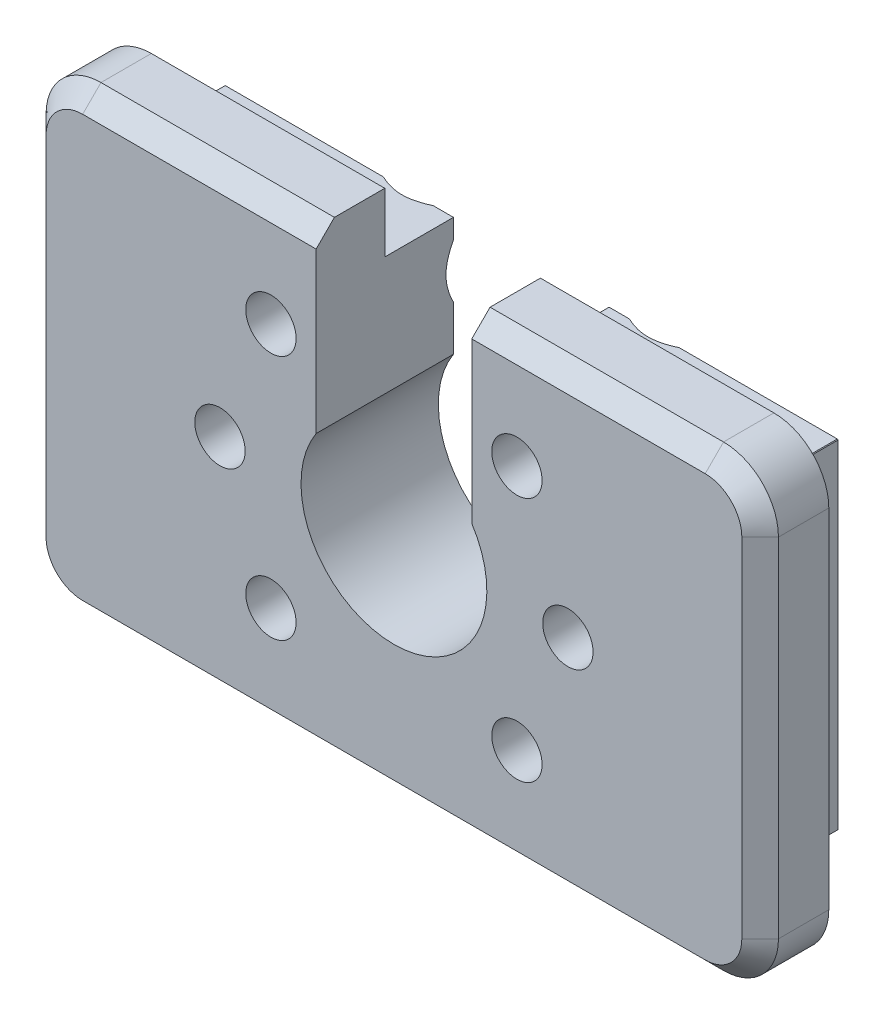
SolidWorks part; units mm, degrees
material "PET"
ref_plane "Front Plane" through (0, 0, 0) normal (0, 0, 1) x (1, 0, 0)
ref_plane "Top Plane" through (0, 0, 0) normal (0, 1, 0) x (1, 0, 0)
ref_plane "Right Plane" through (0, 0, 0) normal (1, 0, 0) x (0, 0, -1)
sketch "Sketch1" plane through (0, 0, 0) normal (0, 0, 1) x (1, 0, 0)
  line L1 (40, -25) -> (-40, -25)
  line L2 (40, -25) -> (40, 25)
  line L3 (40, 25) -> (-40, 25)
  line L4 (-40, -25) -> (-40, 25)
  line L5 (40, -25) -> (-40, 25) construction
  line L6 (40, 25) -> (-40, -25) construction
  point P0 (0, 0)
  dimension "D1" = 50
  dimension "D2" = 80
extrude "Boss-Extrude1" add sketch "Sketch1" against normal blind 7.5
sketch "Sketch2" plane through (0, 0, -7.5) normal (0, 0, -1) x (-1, 0, 0)
  line L8 (33.5, -18.5) -> (33.5, 18.5)
  line L9 (33.5, 18.5) -> (-33.5, 18.5)
  line L10 (-33.5, 18.5) -> (-33.5, -18.5)
  line L11 (-33.5, -18.5) -> (33.5, -18.5)
  line L12 (33.5, -18.5) -> (33.5, 18.5)
  line L13 (33.5, 18.5) -> (-33.5, 18.5)
  line L14 (-33.5, 18.5) -> (-33.5, -18.5)
  line L15 (-33.5, -18.5) -> (33.5, -18.5)
  dimension "D1" = 6.5
extrude "Boss-Extrude2" add sketch "Sketch2" along normal blind 7.5
sketch "Sketch3" plane through (0, 0, 0) normal (0, 0, 1) x (1, 0, 0)
  line L0 (0, 0) -> (0, 51.1675) construction
  line L1 (40, 25) -> (-40, 25) construction
  line L2 (8.5, 5.5473) -> (-8.5, 5.5473) construction
  line L3 (8.5, 5.5473) -> (8.5, 25)
  line L4 (8.5, 25) -> (-8.5, 25)
  line L5 (-8.5, 5.5473) -> (-8.5, 25)
  line L6 (8.5, 5.5473) -> (-8.5, 25) construction
  line L7 (8.5, 25) -> (-8.5, 5.5473) construction
  line L8 (0, 0) -> (-19, 0) construction
  arc A0 (-8.5, 5.5473) -> (8.5, 5.5473) centre (0, 0) ccw
  circle A1 centre (-19, 0) radius 2.75
  circle A2 centre (-13.435, 13.435) radius 2.75
  circle A3 centre (0, 19) radius 2.75 construction
  circle A4 centre (13.435, 13.435) radius 2.75
  circle A5 centre (19, 0) radius 2.75
  circle A6 centre (13.435, -13.435) radius 2.75
  circle A7 centre (0, -19) radius 2.75 construction
  circle A8 centre (-13.435, -13.435) radius 2.75
  point P3 (0, 15.2736)
  point P28 (0, 0)
  dimension "D4" = 5.5
  dimension "D2" = 17
  dimension "D3" = 19
  dimension "D5" = 8
extrude "Cut-Extrude1" cut sketch "Sketch3" against normal through all
fillet "Fillet1" radius 6 4 edges at (40, -25, -3.75) (-40, -25, -3.75) (-40, 25, -3.75) (40, 25, -3.75)
sketch "Sketch4" plane through (0, 0, -15) normal (0, 0, -1) x (-1, 0, 0)
  line L0 (-37, 22) -> (-37, -22) construction
  line L1 (-40, -19) -> (-40, 19) construction
  line L2 (-34, 25) -> (-8.5, 25) construction
  line L4 (34, -25) -> (-34, -25) construction
  line L5 (-37, -22) -> (0, -22) construction
  line L6 (0, 0) -> (0, -22) construction
  circle A0 centre (-37, 22) radius 5
  circle A1 centre (-37, -22) radius 5
  circle A2 centre (-37, 0) radius 2.5
  circle A3 centre (0, -22) radius 2.5
  circle A4 centre (37, -22) radius 5
  circle A5 centre (37, 0) radius 2.5
  circle A6 centre (37, 22) radius 5
  dimension "D4" = 5
  dimension "D5" = 10
  dimension "D1" = 3
  dimension "D2" = 3
  dimension "D3" = 3
extrude "Cut-Extrude2" cut sketch "Sketch4" against normal up to surface (7.5 mm away) up to face at (0, 5.4375, -7.5)
chamfer "Chamfer1" distance 2 angle 45 9 edges at (-21.25, 25, 0) (-38.2426, 23.2426, 0) (-40, 0, 0) (-38.2426, -23.2426, 0) (0, -25, 0) (38.2426, -23.2426, 0) (40, 0, 0) (38.2426, 23.2426, 0) (21.25, 25, 0)
chamfer "Chamfer2" distance 3 angle 45 6 edges at (16.185, -13.435, -15) (-16.25, 0, -15) (-10.685, -13.435, -15) (21.75, 0, -15) (16.185, 13.435, -15) (-10.685, 13.435, -15)
equation "\"hole_radius\"= 10.15mm"
equation "\"D1@Sketch3\"=\"hole_radius\"*2"
equation "\"M5_tap\"=4.2mm"
equation "\"M5_clearence\"=5.5mm"
equation "\"M6_tap\"=5mm"
equation "\"M6_clearence\"=6.6mm"
equation "\"work_area_width\"=1100mm"
equation "\"work_area_depth\"=900mm"
equation "\"steel_base_width\"=80mm"
equation "\"steel_base_height\"=50mm"
equation "\"steel_base_wall_thickness\"=3mm"
equation "\"steel_base_radius\"=6mm"
equation "\"steel_sides_width\"=80mm"
equation "\"steel_sides_height\"=50mm"
equation "\"steel_sides_wall_thickness\"=5mm"
equation "\"steel_sides_radius\"=6mm"
equation "\"steel_gantry_width\"=80mm"
equation "\"steel_gantry_height\"=50mm"
equation "\"steel_gantry_wall_thickness\"=6mm"
equation "\"steel_gantry_radius\"=6mm"
equation "\"steel_rollers_width\"=80mm"
equation "\"steel_rollers_height\"=50mm"
equation "\"steel_rollers_wall_thickness\"=6mm"
equation "\"steel_rollers_radius\"=6mm"
equation "\"steel_zbox_width\"=80mm"
equation "\"steel_zbox_height\"=50mm"
equation "\"steel_zbox_wall_thickness\"=3mm"
equation "\"steel_zbox_radius\"=6mm"
equation "\"D2@Sketch1\"=\"steel_rollers_width\""
equation "\"D1@Sketch1\"=\"steel_rollers_height\""
equation "\"D1@Sketch2\"=\"steel_rollers_wall_thickness\" + 0.5mm"
